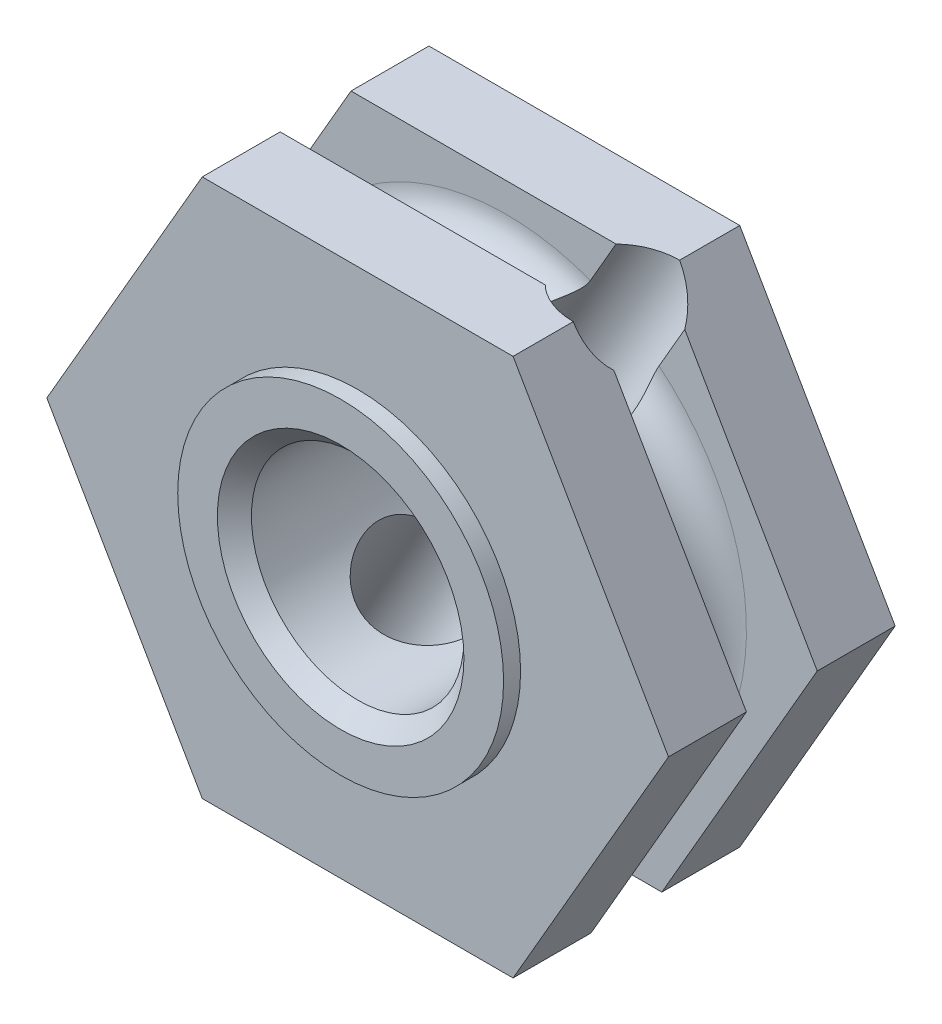
SolidWorks part; units mm, degrees
material "Alloy Steel"
ref_plane "Front Plane" through (0, 0, 0) normal (0, 0, 1) x (1, 0, 0)
ref_plane "Top Plane" through (0, 0, 0) normal (0, 1, 0) x (1, 0, 0)
ref_plane "Right Plane" through (0, 0, 0) normal (1, 0, 0) x (0, 0, -1)
sketch "Sketch1" plane through (0, 0, 0) normal (0, 0, 1) x (1, 0, 0)
  line L1 (-6.9657, 0) -> (-3.4829, -6.0325)
  line L2 (-3.4829, -6.0325) -> (3.4829, -6.0325)
  line L3 (3.4829, -6.0325) -> (6.9657, 0)
  line L4 (6.9657, 0) -> (3.4829, 6.0325)
  line L5 (3.4829, 6.0325) -> (-3.4829, 6.0325)
  line L6 (-3.4829, 6.0325) -> (-6.9657, 0)
  circle A0 centre (0, 0) radius 6.0325 construction
  dimension "D1" = 12.065
extrude "Boss-Extrude1" add sketch "Sketch1" along normal mid plane 5.08
sketch "Sketch2" plane through (0, 0, 2.54) normal (0, 0, 1) x (1, 0, 0)
  circle A0 centre (0, 0) radius 2.3813
  circle A1 centre (0, 0) radius 3.6513
  dimension "D1" = 4.7625
  dimension "D2" = 1.27
extrude "Boss-Extrude2" add sketch "Sketch2" along normal blind 0.381
sketch "Sketch4" plane through (0, 0, 2.54) normal (0, 0, 1) x (1, 0, 0)
  circle A0 centre (0, 0) radius 2.3813 construction
  circle A1 centre (0, 0) radius 2.3813
extrude "Cut-Extrude1" cut sketch "Sketch4" against normal through all
chamfer "Chamfer1" distance 0.381 angle 45 1 edges at (2.3813, 0, 2.921)
ref_plane "Plane1" through (3.4829, 6.0325, 0) normal (-0.5, -0.866, 0) x (0, 0, -1)
sketch "Sketch5" plane through (3.4829, 6.0325, 0) normal (-0.5, -0.866, 0) x (0, 0, -1)
  line L0 (-2.54, 0) -> (2.54, 0) construction
  circle A0 centre (0, 0) radius 1.1913
  dimension "D1" = 2.3825
extrude "Cut-Extrude2" cut sketch "Sketch5" along normal through all
ref_plane "Plane2" through (0, 0, 0) normal (-0.866, 0.5, 0) x (0, 0, 1)
sketch "Sketch6" plane through (0, 0, 0) normal (-0.866, 0.5, 0) x (0, 0, 1)
  line L0 (1.1913, -6.9657) -> (1.1913, -2.3813)
  line L1 (-1.1913, -2.3813) -> (-1.1913, -6.9657)
  line L2 (1.1913, 2.3813) -> (1.1913, 6.9657)
  line L3 (-1.1913, 6.9657) -> (-1.1913, 2.3813)
  line L4 (2.54, -2.3813) -> (2.921, -2.7623)
  line L5 (2.921, 2.7623) -> (2.54, 2.3813)
  line L6 (2.921, 3.6512) -> (2.54, 3.6512)
  line L7 (2.54, -3.6512) -> (2.921, -3.6512)
  line L8 (2.921, 3.6512) -> (2.921, 2.7623)
  line L9 (2.921, -2.7623) -> (2.921, -3.6512)
  line L10 (-2.54, 6.9657) -> (-2.54, 2.3813)
  line L11 (-2.54, -2.3813) -> (-2.54, -6.9657)
  line L12 (2.54, 6.9657) -> (2.54, 3.6512)
  line L13 (2.54, -3.6512) -> (2.54, -6.9657)
  line L14 (-1.1913, -6.9657) -> (-2.54, -6.9657)
  line L15 (2.54, -6.9657) -> (1.1913, -6.9657)
  line L16 (2.54, 2.3813) -> (1.1913, 2.3813)
  line L17 (-1.1913, 2.3813) -> (-2.54, 2.3813)
  line L18 (-2.54, -2.3813) -> (-1.1913, -2.3813)
  line L19 (1.1913, -2.3813) -> (2.54, -2.3813)
  line L20 (2.54, 6.9657) -> (1.1913, 6.9657)
  line L21 (-1.1913, 6.9657) -> (-2.54, 6.9657)
  line L22 (-1.1913, 6.9657) -> (-2.54, 6.9657) construction
  line L23 (2.54, 6.9657) -> (1.1913, 6.9657) construction
  line L24 (1.1913, -2.3813) -> (2.54, -2.3813) construction
  line L25 (-2.54, -2.3813) -> (-1.1913, -2.3813) construction
  line L26 (-1.1913, 2.3813) -> (-2.54, 2.3813) construction
  line L27 (2.54, 2.3813) -> (1.1913, 2.3813) construction
  line L28 (2.54, -6.9657) -> (1.1913, -6.9657) construction
  line L29 (-1.1913, -6.9657) -> (-2.54, -6.9657) construction
  line L30 (2.54, -3.6512) -> (2.54, -6.9657) construction
  line L31 (2.54, 6.9657) -> (2.54, 3.6512) construction
  line L32 (-2.54, -2.3813) -> (-2.54, -6.9657) construction
  line L33 (-2.54, 6.9657) -> (-2.54, 2.3813) construction
  line L34 (2.921, -2.7623) -> (2.921, -3.6512) construction
  line L35 (2.921, 3.6512) -> (2.921, 2.7623) construction
  line L36 (2.54, -3.6512) -> (2.921, -3.6512) construction
  line L37 (2.921, 3.6512) -> (2.54, 3.6512) construction
  line L38 (2.921, 2.7623) -> (2.54, 2.3813) construction
  line L39 (2.54, -2.3813) -> (2.921, -2.7623) construction
  line L40 (-1.1913, 6.9657) -> (-1.1913, 2.3813) construction
  line L41 (1.1913, 2.3813) -> (1.1913, 6.9657) construction
  line L42 (-1.1913, -2.3813) -> (-1.1913, -6.9657) construction
  line L43 (1.1913, -6.9657) -> (1.1913, -2.3813) construction
  line L44 (-0.7937, 6.9657) -> (-0.7937, 5.3782)
  line L45 (-2.794, 6.9657) -> (2.794, 6.9657) construction
  line L46 (0.7937, 5.3782) -> (0.7937, 6.9657)
  line L47 (0.7937, 6.9657) -> (-0.7937, 6.9657)
  arc A0 (-0.7937, 5.3782) -> (0.7937, 5.3782) centre (0, 5.3782) ccw
  point P28 (0, 4.5845)
  dimension "D2" = 0.7937
  dimension "D1" = 1.5875
revolve "Cut-Revolve1" cut sketch "Sketch6" angle 360 about axis through (0, 0, 2.921) along (0, 0, -1)
